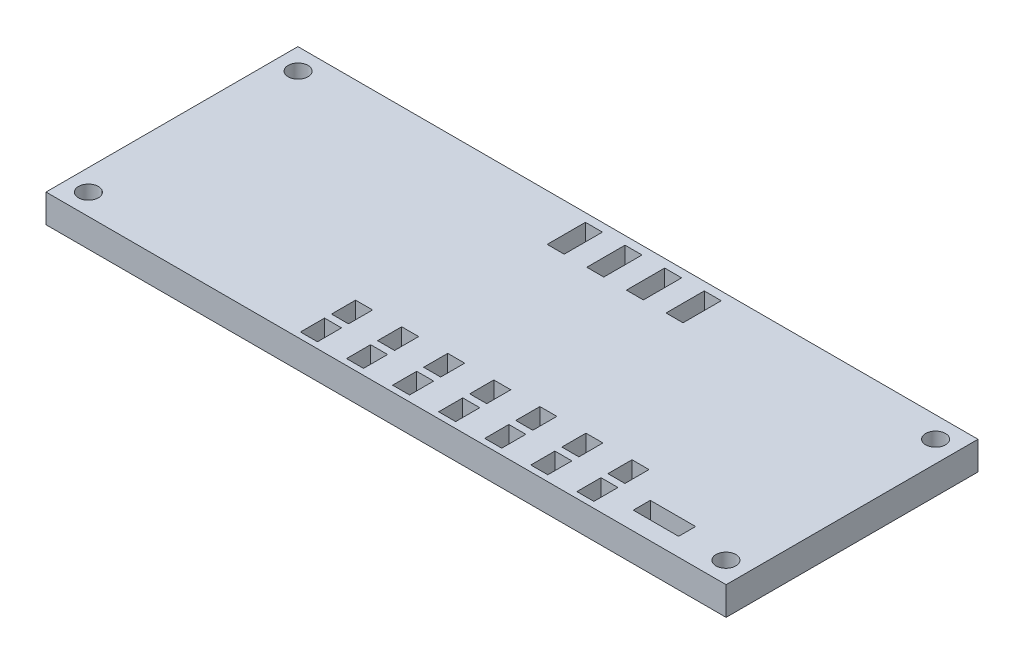
SolidWorks part; units mm, degrees
ref_plane "Front" through (0, 0, 0) normal (0, 0, 1) x (1, 0, 0)
ref_plane "Top" through (0, 0, 0) normal (0, 1, 0) x (1, 0, 0)
ref_plane "Right" through (0, 0, 0) normal (1, 0, 0) x (0, 0, -1)
sketch "草图1" plane through (0, 0, 0) normal (0, 1, 0) x (1, 0, 0)
  line L1 (-60.0075, 22.225) -> (60.0075, 22.225)
  line L2 (-60.0075, 22.225) -> (-60.0075, -22.225)
  line L3 (-60.0075, -22.225) -> (60.0075, -22.225)
  line L4 (60.0075, 22.225) -> (60.0075, -22.225)
  line L5 (-60.0075, 22.225) -> (60.0075, -22.225) construction
  line L6 (-60.0075, -22.225) -> (60.0075, 22.225) construction
  point P0 (0, 0)
  dimension "D1" = 44.45
  dimension "D2" = 120.015
extrude "凸台-拉伸1" add sketch "草图1" along normal blind 5 contours L2 L3 L4 L1
sketch "草图2" plane through (0, 0, 0) normal (0, 1, 0) x (1, 0, 0)
  circle A0 centre (-56.25, 18.5) radius 1.75
  dimension "D1" = 3.5
  dimension "D2" = 56.25
  dimension "D3" = 18.5
extrude "切除-拉伸4" cut sketch "草图2" along normal blind 5 contours A0
mirror "镜向1" about plane through (0, 0, 0) normal (0, 0, 1) of "切除-拉伸4"
mirror "镜向2" about plane through (0, 0, 0) normal (1, 0, 0) of "镜向1"
ref_plane "基准面1" through (-60.0075, 0, -22.225) normal (1, 0, 0) x (0, 0, -1)
sketch "草图3" plane through (0, 5, 0) normal (0, 1, 0) x (1, 0, 0)
  line L1 (-16.1685, -11.433) -> (-13.1685, -11.433)
  line L2 (-16.1685, -11.433) -> (-16.1685, -15.683)
  line L3 (-16.1685, -15.683) -> (-13.1685, -15.683)
  line L4 (-13.1685, -11.433) -> (-13.1685, -15.683)
  circle A0 centre (-14.6685, -12.933) radius 0.25 construction
  circle A1 centre (-14.6685, -14.183) radius 0.25 construction
  dimension "D3" = 1.5
  dimension "D4" = 1.5
  dimension "D1" = 1.5
  dimension "D2" = 1.5
extrude "切除-拉伸5" cut sketch "草图3" against normal blind 5
pattern_linear "阵列(线性)1" count 7 spacing 8.13 along (1, 0, 0) count 2 spacing 5.48 along (0, 0, 1) of "切除-拉伸5"
sketch "草图4" plane through (0, 5, 0) normal (0, 1, 0) x (1, 0, 0)
  line L1 (-7.7865, 20.744) -> (-4.7865, 20.744)
  line L2 (-7.7865, 20.744) -> (-7.7865, 13.994)
  line L3 (-7.7865, 13.994) -> (-4.7865, 13.994)
  line L4 (-4.7865, 20.744) -> (-4.7865, 13.994)
  circle A0 centre (-6.2865, 19.244) radius 0.25 construction
  circle A1 centre (-6.2865, 15.494) radius 0.25 construction
  dimension "D1" = 1.5
  dimension "D2" = 1.5
  dimension "D4" = 1.5
  dimension "D3" = 1.5
extrude "切除-拉伸6" cut sketch "草图4" against normal blind 5
pattern_linear "阵列(线性)2" count 4 spacing 6.99 along (1, 0, 0) of "切除-拉伸6"
sketch "草图5" plane through (0, 5, 0) normal (0, 1, 0) x (1, 0, 0)
  line L1 (40.4265, -16.026) -> (48.4265, -16.026)
  line L2 (40.4265, -16.026) -> (40.4265, -19.026)
  line L3 (40.4265, -19.026) -> (48.4265, -19.026)
  line L4 (48.4265, -16.026) -> (48.4265, -19.026)
  circle A0 centre (41.9265, -17.526) radius 0.25 construction
  circle A1 centre (46.9265, -17.526) radius 0.25 construction
  dimension "D1" = 1.5
  dimension "D2" = 1.5
  dimension "D3" = 1.5
  dimension "D4" = 1.5
extrude "切除-拉伸7" cut sketch "草图5" against normal blind 5
